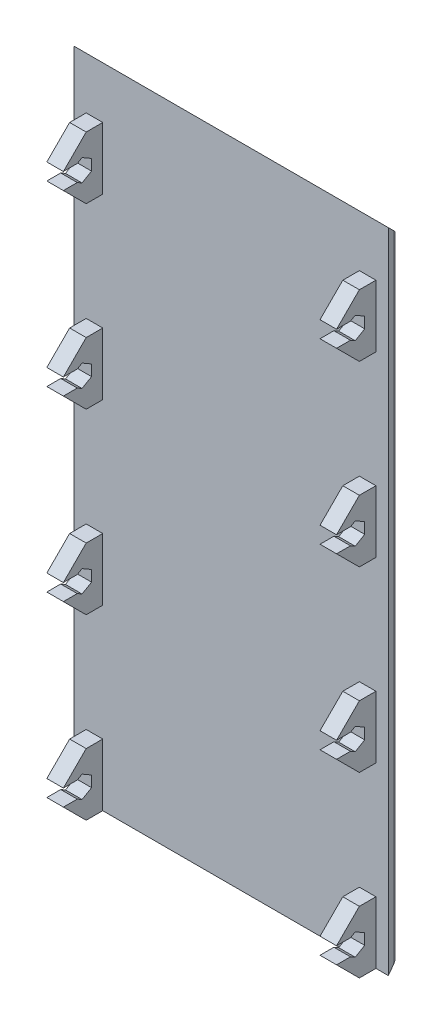
SolidWorks part; units mm, degrees
ref_plane "Front Plane" through (0, 0, 0) normal (0, 0, 1) x (1, 0, 0)
ref_plane "Top Plane" through (0, 0, 0) normal (0, 1, 0) x (1, 0, 0)
ref_plane "Right Plane" through (0, 0, 0) normal (1, 0, 0) x (0, 0, -1)
sketch "Sketch1" plane through (0, 0, 0) normal (0, 1, 0) x (1, 0, 0)
  line L0 (-9.2151, 0) -> (-9.2151, -10)
  line L1 (-9.2151, -10) -> (-5.2151, -10)
  line L2 (-5.2151, -10) -> (-5.2151, 0)
  line L3 (-5.2151, 0) -> (56.7849, 0)
  line L4 (56.7849, 0) -> (56.7849, -10)
  line L5 (56.7849, -10) -> (60.7849, -10)
  line L6 (60.7849, -10) -> (60.7849, 0)
  line L7 (60.7849, 0) -> (63.7849, 0)
  line L8 (-9.2151, 0) -> (-12.2151, 0)
  line L9 (-12.2151, 0) -> (-8.1737, 7)
  line L10 (-8.1737, 7) -> (59.7434, 7)
  line L11 (59.7434, 7) -> (63.7849, 0)
  line L12 (25.7849, 7) -> (25.7849, 0) construction
  dimension "D1" = 3
  dimension "D2" = 10
  dimension "D3" = 70
  dimension "D4" = 7
  dimension "D5" = 4
  dimension "D6" = 60
extrude "Boss-Extrude1" add sketch "Sketch1" along normal blind 156.5
sketch "Sketch4" plane through (60.7849, 0, 0) normal (1, 0, 0) x (0, 0, -1)
  line L0 (0, 156.5) -> (0, 0) construction
  line L1 (-37.5185, 156.5) -> (0, 156.5)
  line L2 (-37.5185, 156.5) -> (-37.5185, 144)
  line L3 (-37.5185, 144) -> (0, 144)
  line L4 (0, 156.5) -> (0, 144)
  line L5 (-37.5185, 156.5) -> (0, 144) construction
  line L6 (-37.5185, 144) -> (0, 156.5) construction
  line L7 (-10, 156.5) -> (0, 156.5) construction
  point P0 (-18.7592, 150.25)
  dimension "D1" = 12.5
extrude "Cut-Extrude1" cut sketch "Sketch4" against normal through all
sketch "Sketch5" plane through (60.7849, 0, 0) normal (1, 0, 0) x (0, 0, -1)
  line L0 (0, 156.5) -> (0, 0) construction
  line L1 (-33.3149, 129) -> (0, 129)
  line L2 (-33.3149, 129) -> (-33.3149, 101)
  line L3 (-33.3149, 101) -> (0, 101)
  line L4 (0, 129) -> (0, 101)
  line L5 (-33.3149, 129) -> (0, 101) construction
  line L6 (-33.3149, 101) -> (0, 129) construction
  line L7 (-10, 144) -> (0, 144) construction
  point P0 (-16.6574, 115)
  dimension "D1" = 28
  dimension "D2" = 15
extrude "Cut-Extrude2" cut sketch "Sketch5" against normal through all
sketch "Sketch6" plane through (0, 0, 0) normal (1, 0, 0) x (0, 0, -1)
  line L0 (-10, 144) -> (-10, 129) construction
  line L1 (-2.7, 137.8279) -> (-5, 139.1558)
  line L2 (-5, 139.1558) -> (-7.3, 137.8279)
  line L3 (-7.3, 137.8279) -> (-7.3, 135.1721)
  line L4 (-7.3, 135.1721) -> (-5, 133.8442)
  line L5 (-5, 133.8442) -> (-2.7, 135.1721)
  line L6 (-2.7, 135.1721) -> (-2.7, 137.8279)
  line L7 (-10, 144) -> (0, 144) construction
  line L8 (-6.15, 138.4919) -> (-10, 138.4919)
  line L9 (-6.15, 134.5081) -> (-10, 134.5081)
  line L10 (-10, 134.5081) -> (-10, 138.4919)
  circle A1 centre (-5, 136.5) radius 2.3 construction
  dimension "D1" = 4.6
  dimension "D2" = 7.5
  dimension "D3" = 5
extrude "Cut-Extrude3" cut sketch "Sketch6" against normal through all and the other way through all contours L10 L9 L4 L3 L2 L8 | L5 L6 L1 L2 L3 L4 region at (0, 136.5, 5) region at (0, 136.5, 8.5351)
pattern_linear "LPattern1" count 4 spacing 43 along (0, -1, 0) of "Cut-Extrude2", "Cut-Extrude3"
chamfer "Chamfer3" distance 7 angle 45 1 edges at (25.7849, 156.5, -7)
fillet "Fillet1" radius 8 2 edges at (-8.1737, 74.75, -7) (59.7434, 74.75, -7)
chamfer "Chamfer5" distance 6 angle 45 16 edges at (58.7849, 43, 10) (58.7849, 144, 10) (58.7849, 129, 10) (-7.2151, 144, 10) (-7.2151, 129, 10) (-7.2151, 101, 10) (-7.2151, 86, 10) (58.7849, 101, 10) (58.7849, 86, 10) (58.7849, 58, 10) (58.7849, 0, 10) (58.7849, 15, 10) (-7.2151, 0, 10) (-7.2151, 15, 10) (-7.2151, 58, 10) (-7.2151, 43, 10)
sketch "Sketch7" plane through (0, 0, -7) normal (0, 0, -1) x (-1, 0, 0)
  line L0 (-5.7651, 110.3803) -> (-45.7651, 110.3803) construction
  line L1 (-5.7651, 110.3803) -> (-5.7651, 32.6805) construction
  line L2 (-45.7651, 110.3803) -> (-45.7651, 32.6805) construction
  line L3 (-5.7651, 32.6805) -> (-45.7651, 32.6805) construction
  line L4 (-5.7651, 110.3803) -> (-5.7651, 103.3803)
  line L5 (-5.7651, 110.3803) -> (-45.7651, 110.3803)
  line L6 (-5.7651, 103.3803) -> (-45.7651, 103.3803)
  line L7 (-45.7651, 110.3803) -> (-45.7651, 103.3803)
  line L8 (3.5549, 0) -> (3.5549, 149.5) construction
  line L9 (-5.7651, 95.2974) -> (-45.7651, 72.2034)
  line L10 (-5.7651, 103.3803) -> (-25.7651, 91.8333)
  line L11 (-25.7651, 91.8333) -> (-45.7651, 103.3803)
  line L12 (-19.7651, 103.3803) -> (-25.7651, 99.9162)
  line L13 (-25.7651, 99.9162) -> (-31.7651, 103.3803)
  line L14 (-25.7651, 99.9162) -> (-25.7651, 91.8333) construction
  line L15 (-5.7651, 95.2974) -> (-5.7651, 74.2233)
  line L16 (-45.7651, 72.2034) -> (-45.7651, 64.1205)
  line L17 (-45.7651, 64.1205) -> (-23.7651, 76.8222)
  line L18 (-23.7651, 76.8222) -> (-23.7651, 74.2233)
  line L19 (-11.7651, 91.8333) -> (-11.7651, 74.2233)
  line L20 (-5.7651, 74.2233) -> (-23.7651, 74.2233) construction
  line L21 (-17.7651, 88.3692) -> (-17.7651, 74.2233)
  line L22 (-11.7651, 74.2233) -> (-17.7651, 74.2233) construction
  line L23 (-35.2962, 97.3361) -> (-45.7651, 91.2919)
  line L24 (-45.7651, 91.2919) -> (-45.7651, 84.2919)
  line L25 (-45.7651, 84.2919) -> (-35.2962, 78.2476)
  line L26 (-28.2962, 93.2946) -> (-37.8273, 87.7919)
  line L27 (-37.8273, 87.7919) -> (-28.2962, 82.2891)
  arc A0 (-5.7651, 74.2233) -> (-23.7651, 74.2233) centre (-14.7651, 74.2233) cw
  arc A1 (-11.7651, 74.2233) -> (-17.7651, 74.2233) centre (-14.7651, 74.2233) cw
  dimension "D11" = 6
  dimension "D12" = 7
  dimension "D1" = 40
  dimension "D2" = 9.32
  dimension "D3" = 7
  dimension "D4" = 30
  dimension "D5" = 30
  dimension "D6" = 7
  dimension "D7" = 7
  dimension "D8" = 7
  dimension "D9" = 6
  dimension "D10" = 6
  dimension "D13" = 7
  dimension "D14" = 30
  dimension "D15" = 30
  dimension "D16" = 7
extrude "Cut-Extrude4" cut sketch "Sketch7" against normal blind 1 contours L5 L7 L6 L4 | L12 L13 L6 L11 L10 | L27 L26 L11 L23 L24 L25 L9 | L19 A1 L21 L9 L16 L17 L18 A0 L15 region at (25.7651, 106.8803, -7) region at (25.7651, 99.2649, -7) region at (33.1911, 90.7673, -7) region at (21.5908, 76.662, -7)
